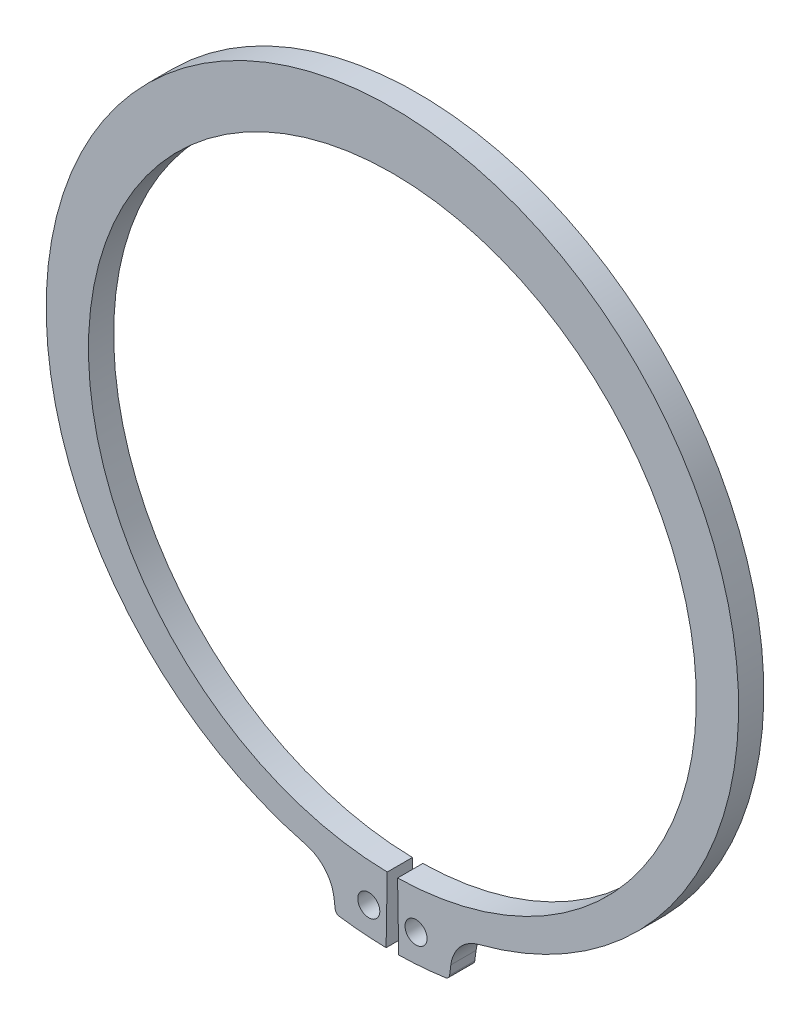
SolidWorks part; units mm, degrees
ref_plane "Plane1" through (0, 0, 0) normal (0, 0, 1) x (1, 0, 0)
ref_plane "Plane2" through (0, 0, 0) normal (0, 1, 0) x (1, 0, 0)
ref_plane "Plane3" through (0, 0, 0) normal (1, 0, 0) x (0, 0, -1)
sketch "Clipboard" plane through (0, 0, 0) normal (0, 0, 1) x (1, 0, 0)
  line L0 (0, 0) -> (9, 0)
  line L1 (0, 0) -> (0, 4.5)
  line L2 (0, 0) -> (0, -10.5)
  circle A0 centre (0, 0) radius 1.75
  circle A1 centre (0, 0) radius 50
  dimension "HoleDia" = 3.5
sketch "BodySke" plane through (0, 0, 0) normal (0, 0, 1) x (1, 0, 0)
  line L0 (-1.5431, 0) -> (1.5431, 0) construction
  line L1 (0, 0) -> (0, 57.25) construction
  line L2 (0.8213, -48.243) -> (1, -58.7415)
  line L3 (-0.8213, -48.243) -> (-1, -58.7415)
  line L4 (0, 0) -> (15.2272, -56.7424) construction
  line L5 (0, 0) -> (-15.2272, -56.7424) construction
  line L7 (9.2788, -55.9592) -> (9.0765, -57.4962)
  line L8 (-9.2788, -55.9592) -> (-9.0765, -57.4962)
  circle A0 centre (0, 0) radius 48.25 construction
  arc A1 (0.8213, -48.243) -> (-0.8213, -48.243) centre (0, 0) ccw
  arc A2 (13.672, -50.9474) -> (-13.672, -50.9474) centre (0, 2.2875) ccw construction
  arc A3 (1, -58.7415) -> (8.4406, -58.1405) centre (0, 0) ccw
  arc A4 (13.7286, -50.9329) -> (9.2788, -55.9592) centre (15.2272, -56.7424) ccw
  arc A5 (-9.2788, -55.9592) -> (-13.7286, -50.9329) centre (-15.2272, -56.7424) ccw
  arc A6 (-8.4406, -58.1405) -> (-1, -58.7415) centre (0, 0) ccw
  arc A7 (13.7286, -50.9329) -> (-13.7286, -50.9329) centre (0, 2.2875) ccw
  arc A8 (-9.5998, -53.5209) -> (9.5998, -53.5209) centre (0, 0) ccw construction
  circle A9 centre (3.75, -54.2455) radius 1.75
  circle A10 centre (-3.75, -54.2455) radius 1.75
  arc A11 (9.0765, -57.4962) -> (8.4406, -58.1405) centre (8.3329, -57.3983) cw
  arc A12 (-9.0765, -57.4962) -> (-8.4406, -58.1405) centre (-8.3329, -57.3983) ccw
  point P28 (9.0027, -58.0561)
  point P31 (-9.0027, -58.0561)
  dimension "HoleDia" = 3.5
  dimension "D3" = 0.75
  dimension "D2" = 15
  dimension "Gap" = 2
extrude "Body" add sketch "BodySke" against normal blind 4
sketch "NotSke" plane through (0, 0, 0) normal (0, 0, 1) x (1, 0, 0)
  line L0 (3.75, -52.4955) -> (3.75, -55.9955)
  line L1 (3.75, -55.9955) -> (-3.75, -55.9955)
  line L2 (-3.75, -55.9955) -> (-3.75, -52.4955)
  line L3 (-3.75, -52.4955) -> (3.75, -52.4955)
  circle A0 centre (3.75, -54.2455) radius 1.75 construction
  circle A1 centre (-3.75, -54.2455) radius 1.75 construction
extrude "Notch" [suppressed] cut sketch "NotSke" against normal through all
sketch "UnlSke" plane through (0, 0, 0) normal (0, 0, 1) x (1, 0, 0)
  line L0 (-5.9359, -58.4494) -> (-4.875, -48.0031)
  line L1 (5.9359, -58.4494) -> (4.875, -48.0031)
  arc A0 (4.875, -48.0031) -> (-4.875, -48.0031) centre (0, 0) ccw
  arc A1 (5.9359, -58.4494) -> (-5.9359, -58.4494) centre (0, 0) ccw
  arc A2 (1, -58.7415) -> (8.4406, -58.1405) centre (0, 0) ccw construction
  arc A3 (0.8213, -48.243) -> (-0.8213, -48.243) centre (0, 0) ccw construction
  circle A4 centre (-3.75, -54.2455) radius 1.75 construction
  circle A5 centre (3.75, -54.2455) radius 1.75 construction
extrude "Unlug" [suppressed] add sketch "UnlSke" against normal through all
equation "' \"ShaftDia@Clipboard\" = 15"
equation "' \"Thickness@Body\" = 1.5"
equation "' \"GrooveDia@BodySke\" = 14.3"
equation "' \"LugSection@Clipboard\" = 4.8"
equation "' \"LargeSection@Clipboard\" = 2.4"
equation "' \"HoleDia@Clipboard\" = 2.0"
equation "' \"ShaftDia@Clipboard\" = 50"
equation "' \"Thickness@Body\" = 3"
equation "' \"GrooveDia@BodySke\" = 47"
equation "' \"LugSection@Clipboard\" = 8"
equation "' \"LargeSection@Clipboard\" = 5.1"
equation "' \"HoleDia@Clipboard\" = 2.5"
equation "\"SmallSection@Clipboard\" = \"LargeSection@Clipboard\" * 0.5"
equation "\"Gap@BodySke\" =  \"Thickness@Body\" / 2"
equation "\"LargeRad@BodySke\" =  \"GrooveDia@BodySke\" / 2 +  \"LargeSection@Clipboard\""
equation "\"SmallRad@BodySke\" =  \"GrooveDia@BodySke\" / 2 +  \"SmallSection@Clipboard\""
equation "\"LugRad@BodySke\" = \"GrooveDia@BodySke\" / 2 + \"LugSection@Clipboard\""
equation "\"HoleOffsetRad@BodySke\" = (  \"ShaftDia@Clipboard\" / 2 + \"LugRad@BodySke\" ) / 2"
equation "\"HoleSpacing@BodySke\" = \"Gap@BodySke\"  * 2 +  \"HoleDia@Clipboard\""
equation "\"HoleDia@BodySke\" =  \"HoleDia@Clipboard\""
equation "\"SmallAngle@BodySke\" = atn(\"HoleSpacing@BodySke\" / 2 / sqr(\"HoleOffsetRad@BodySke\"  * \"HoleOffsetRad@BodySke\" - (\"HoleSpacing@BodySke\" / 2) * (\"HoleSpacing@BodySke\" / 2) ))  * 7 *  (\"LargeRad@BodySke\" / \"SmallRad@BodySke\")* ( 180 / 3.141593)"
